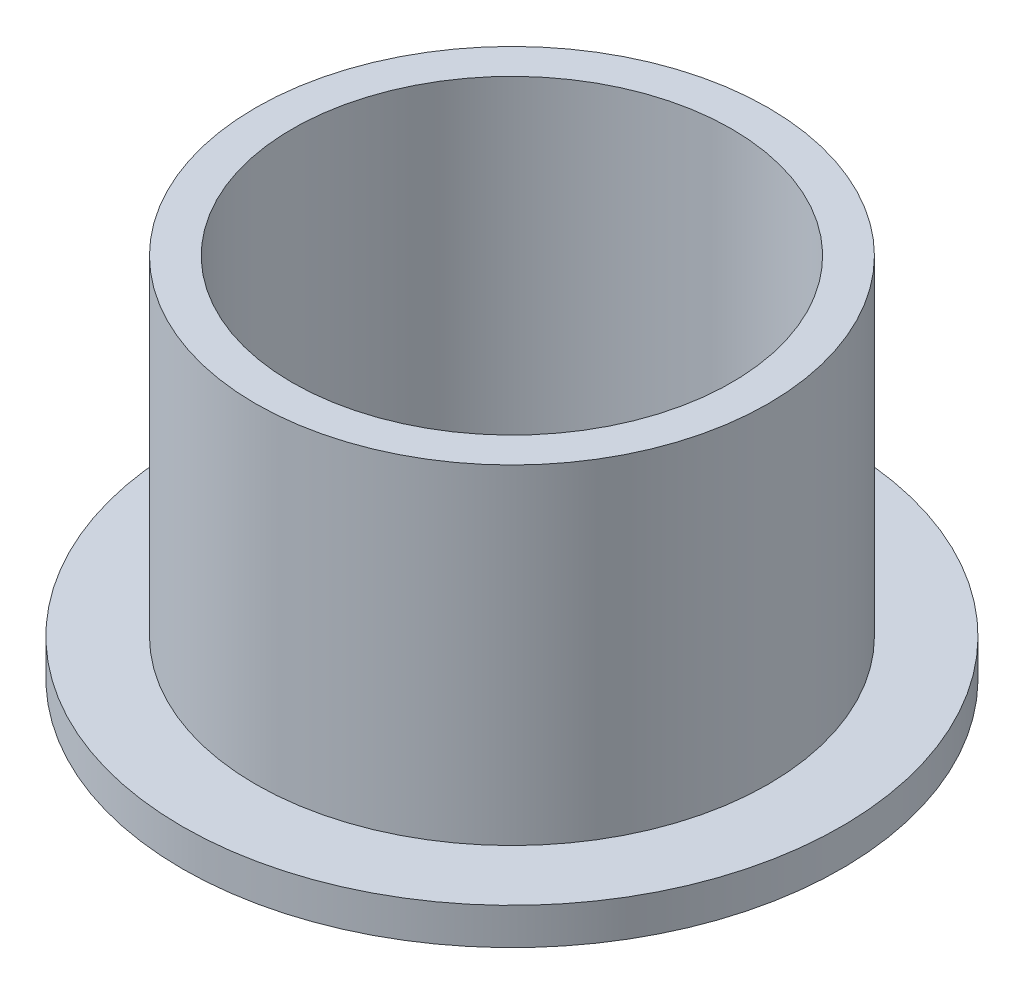
SolidWorks part; units mm, degrees
material "Polyethylene Cross-Linked"
ref_plane "Front" through (0, 0, 0) normal (0, 0, 1) x (1, 0, 0)
ref_plane "Top" through (0, 0, 0) normal (0, 1, 0) x (1, 0, 0)
ref_plane "Right" through (0, 0, 0) normal (1, 0, 0) x (0, 0, -1)
sketch "Sketch1" plane through (0, 0, 0) normal (0, 1, 0) x (1, 0, 0)
  line L0 (0, 6) -> (0, 7) construction
  circle A0 centre (0, 0) radius 6
  circle A1 centre (0, 0) radius 7
  circle A2 centre (0, 0) radius 9
  point P7 (0, 6.3333)
  dimension "ID" = 12
  dimension "OD" = 14
  dimension "FlangeOD" = 18
  dimension "D1" = 1
  dimension "D2" = 0.3333
sketch "Sketch2" plane through (0, 0, 0) normal (0, 1, 0) x (1, 0, 0)
  circle A0 centre (0, 0) radius 6 construction
  circle A1 centre (0, 0) radius 7 construction
  circle A2 centre (0, 0) radius 6
  circle A3 centre (0, 0) radius 7
extrude "Boss-Extrude1" add sketch "Sketch2" along normal blind 10
sketch "Sketch3" plane through (0, 0, 0) normal (0, 1, 0) x (1, 0, 0)
  circle A0 centre (0, 0) radius 9 construction
  circle A1 centre (0, 0) radius 7 construction
  circle A2 centre (0, 0) radius 9
  circle A3 centre (0, 0) radius 7
extrude "Boss-Extrude2" add sketch "Sketch3" along normal blind 1
sketch "Sketch4" plane through (0, 0, 0) normal (1, 0, 0) x (0, 0, -1)
  line L0 (0, 0) -> (0, 10) construction
  line L1 (9, 0) -> (9, 1) construction
  line L3 (6.1524, 10) -> (6.0762, 10)
  line L4 (6.0762, 0.0762) -> (6.0762, 10)
  line L5 (6.0762, 0.0762) -> (9, 0.0762)
  line L6 (9, 0.0762) -> (9, 0.1524)
  line L7 (9, 0.1524) -> (6.1524, 0.1524)
  line L8 (6.1524, 0.1524) -> (6.1524, 10)
  line L9 (-9, 0) -> (9, 0) construction
  line L10 (7, 10) -> (-7, 10) construction
  line L12 (6, 10) -> (6, 0) construction
  line L13 (6, 10) -> (-6, 10) construction
  dimension "D1" = 0.0762
  dimension "D2" = 0.0762
  dimension "D3" = 0.0762
ref_plane "Contact Plane 1" through (0, 10, 0) normal (0, 1, 0) x (1, 0, 0)
ref_plane "Contact Plane 2" through (0, 0, 0) normal (0, -1, 0) x (-1, 0, 0)
ref_axis "Center Axis 1" through (0, 10, 0) along (0, -1, 0)
equation "\"D2@Sketch1\" = \"D1@Sketch1\"/3"
